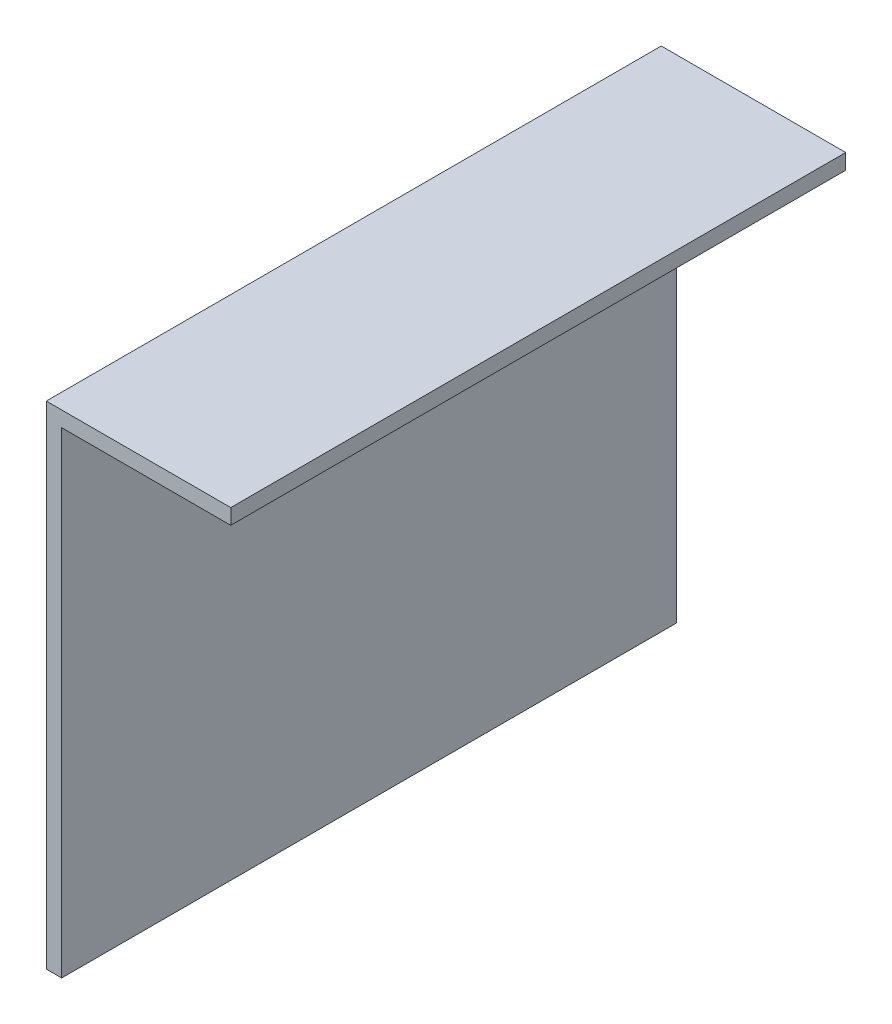
SolidWorks part; units mm, degrees
ref_plane "Front Plane" through (0, 0, 0) normal (0, 0, 1) x (1, 0, 0)
ref_plane "Top Plane" through (0, 0, 0) normal (0, 1, 0) x (1, 0, 0)
ref_plane "Right Plane" through (0, 0, 0) normal (1, 0, 0) x (0, 0, -1)
sketch "Sketch1" plane through (0, 0, 0) normal (0, 0, 1) x (1, 0, 0)
  line L0 (1.5875, 47.625) -> (36.5125, 47.625)
  line L1 (1.5875, -50.8) -> (-1.5875, -50.8)
  line L2 (1.5875, -50.8) -> (1.5875, 47.625)
  line L4 (-1.5875, -50.8) -> (-1.5875, 50.8)
  line L5 (1.5875, -50.8) -> (-1.5875, 50.8) construction
  line L6 (3.5127, 112.4075) -> (-1.5875, -50.8) construction
  line L7 (-1.5875, 50.8) -> (36.5125, 50.8)
  line L10 (36.5125, 50.8) -> (36.5125, 47.625)
  point P0 (0, 0)
  point P7 (0, -50.8)
  point P10 (1.5875, -50.8)
  dimension "D1" = 3.175
  dimension "D2" = 3.175
  dimension "D3" = 38.1
  dimension "D4" = 101.6
extrude "Boss-Extrude1" add sketch "Sketch1" along normal blind 127
equation "\"eighthinch\"= 0.125"
equation "\"D2@Sketch1\"=\"eighthinch\""
